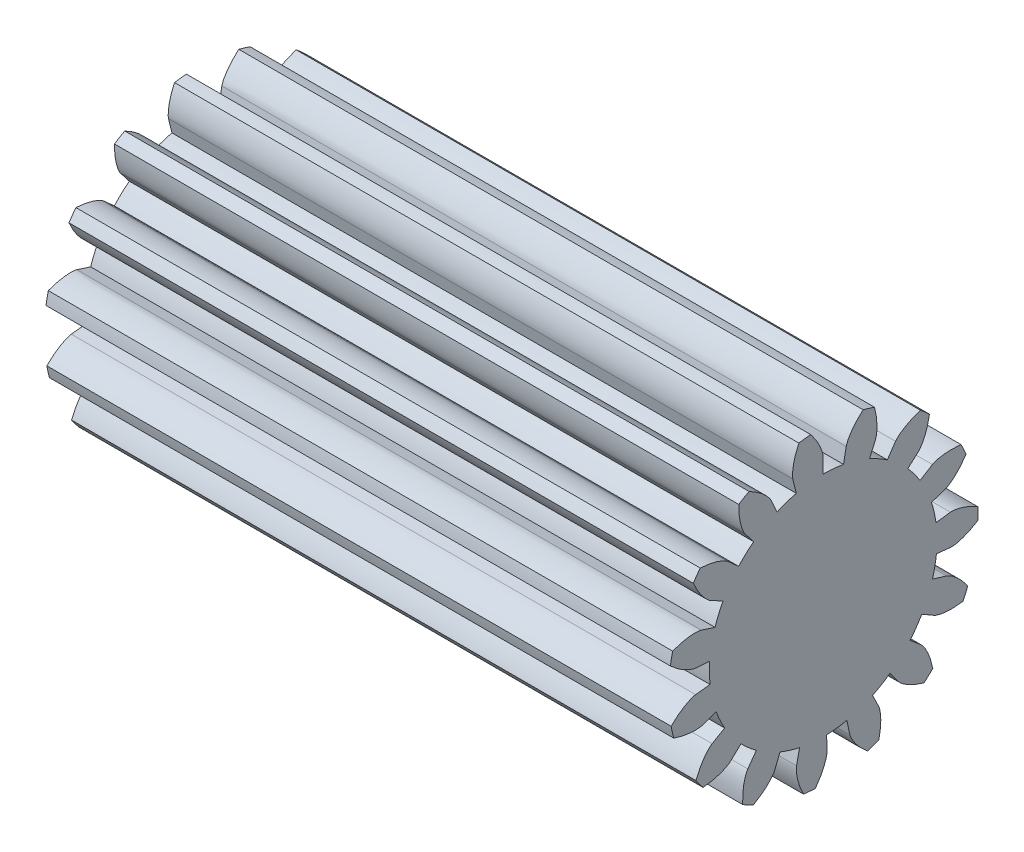
SolidWorks part; units mm, degrees
ref_plane "Front Plane" through (0, 0, 0) normal (1, 0, 0) x (0, 1, 0)
ref_plane "Top Plane" through (0, 0, 0) normal (0, 0, 1) x (0, 1, 0)
ref_plane "Right Plane" through (0, 0, 0) normal (0, 1, 0) x (-1, 0, 0)
sketch "Sketch1" plane through (0, 0, 0) normal (1, 0, 0) x (0, 1, 0)
  circle A0 centre (0, 0) radius 2.8333
  circle A1 centre (0, 0) radius 2.3492 construction
  circle A2 centre (0, 0) radius 2.0833 construction
  circle A3 centre (0, 0) radius 2.5 construction
  dimension "D1" = 5.6667
  dimension "D2" = 4.6985
  dimension "D3" = 4.1667
  dimension "D4" = 5
extrude "Boss-Extrude1" add sketch "Sketch1" along normal blind 11.43
sketch "Sketch3" plane through (11.43, 0, 0) normal (1, 0, 0) x (0, 1, 0)
  line L0 (0, 0) -> (2.3492, 0) construction
  line L1 (0, 0) -> (2.4997, 0.0373) construction
  line L2 (0, 0) -> (2.4899, -0.2242) construction
  line L3 (2.4899, -0.2242) -> (2.3398, -0.2107)
  line L4 (2.4899, -0.2242) -> (3.2461, -0.2923)
  line L5 (3.2461, 0.7075) -> (3.2461, -0.2923)
  line L6 (2.3492, 0) -> (2.0833, 0)
  line L7 (2.3398, -0.2107) -> (2.0749, -0.1869)
  circle A0 centre (0, 0) radius 2.5 construction
  circle A1 centre (0, 0) radius 2.3492 construction
  circle A2 centre (0, 0) radius 2.0833 construction
  arc A3 (2.0833, 0) -> (2.0749, -0.1869) centre (0, 0) cw
  spline S0 degree 4 poles (2.3492, 0) (2.351, 0) (2.3558, 0.0003) (2.3708, 0.0017) (2.4002, 0.0065) (2.436, 0.0154) (2.4766, 0.0283) (2.5151, 0.043) (2.5477, 0.0568) (2.5797, 0.0719) (2.6112, 0.0879) (2.6488, 0.1086) (2.6932, 0.1351) (2.7439, 0.1686) (2.7998, 0.2094) (2.8551, 0.254) (2.908, 0.3003) (2.9597, 0.3497) (3.0083, 0.3994) (3.0568, 0.4536) (3.1005, 0.5049) (3.1472, 0.5652) (3.1841, 0.6146) (3.2302, 0.6825) (3.2566, 0.7234) (3.2865, 0.7723) (3.2993, 0.7944) (3.3072, 0.808) knots 0 0 0 0 0 0.005377 0.015084 0.04661 0.092111 0.119476 0.146842 0.174209 0.201575 0.228941 0.256307 0.307035 0.361767 0.4165 0.471232 0.525964 0.580697 0.635429 0.690161 0.744894 0.799626 0.854358 0.909091 0.954545 1 1 1 1 1 construction
  spline S1 degree 4 poles (2.3492, 0) (2.351, 0) (2.3558, 0.0003) (2.3708, 0.0017) (2.4002, 0.0065) (2.436, 0.0154) (2.4766, 0.0283) (2.5151, 0.043) (2.5477, 0.0568) (2.5797, 0.0719) (2.6112, 0.0879) (2.6488, 0.1086) (2.6932, 0.1351) (2.7439, 0.1686) (2.7998, 0.2094) (2.8551, 0.254) (2.908, 0.3003) (2.9597, 0.3497) (3.0083, 0.3994) (3.0568, 0.4536) (3.1005, 0.5049) (3.1472, 0.5652) (3.1841, 0.6146) (3.2202, 0.6678) (3.2374, 0.694) (3.2461, 0.7075) knots 0 0 0 0 0 0.005377 0.015084 0.04661 0.092111 0.119476 0.146842 0.174209 0.201575 0.228941 0.256307 0.307035 0.361767 0.4165 0.471232 0.525964 0.580697 0.635429 0.690161 0.744894 0.799626 0.854358 0.909091 0.909091 0.909091 0.909091 0.909091
extrude "Cut-Extrude1" cut sketch "Sketch3" against normal through all
mirror "Mirror1" about plane through (0, 2.4899, -0.2242) normal (0, -0.0897, -0.996) of "Cut-Extrude1"
pattern_circular "CirPattern6" count 15 over 360 about axis through (11.43, 0, 0) along (-1, 0, 0) of "Cut-Extrude1", "Mirror1"
equation "\"DiametralPitch\"= 3"
equation "\"NumberTeeth\"= 15"
equation "\"PressureAngle\"= 20"
equation "\"PitchDiameter\"= \"NumberTeeth\" / \"DiametralPitch\""
equation "\"BaseDiameter\"= \"PitchDiameter\" * cos ( \"PressureAngle\" )"
equation "\"Addendum\"= 1 / \"DiametralPitch\""
equation "\"Dedendum\"= 1.25 / \"DiametralPitch\""
equation "\"AddendumDiameter\"= \"PitchDiameter\" + \"Addendum\" + \"Addendum\""
equation "\"DedendumDiameter\"= \"PitchDiameter\" - \"Dedendum\" - \"Dedendum\""
equation "\"ToothSpacing\"= 360 / ( 4 * \"NumberTeeth\" )"
equation "\"D1@Sketch1\"=\"AddendumDiameter\""
equation "\"D2@Sketch1\"=\"BaseDiameter\""
equation "\"D3@Sketch1\"=\"DedendumDiameter\""
equation "\"D4@Sketch1\"=\"PitchDiameter\""
equation "\"D1@Sketch3\"=\"ToothSpacing\""
equation "\"D1@CirPattern6\"=\"NumberTeeth\""
